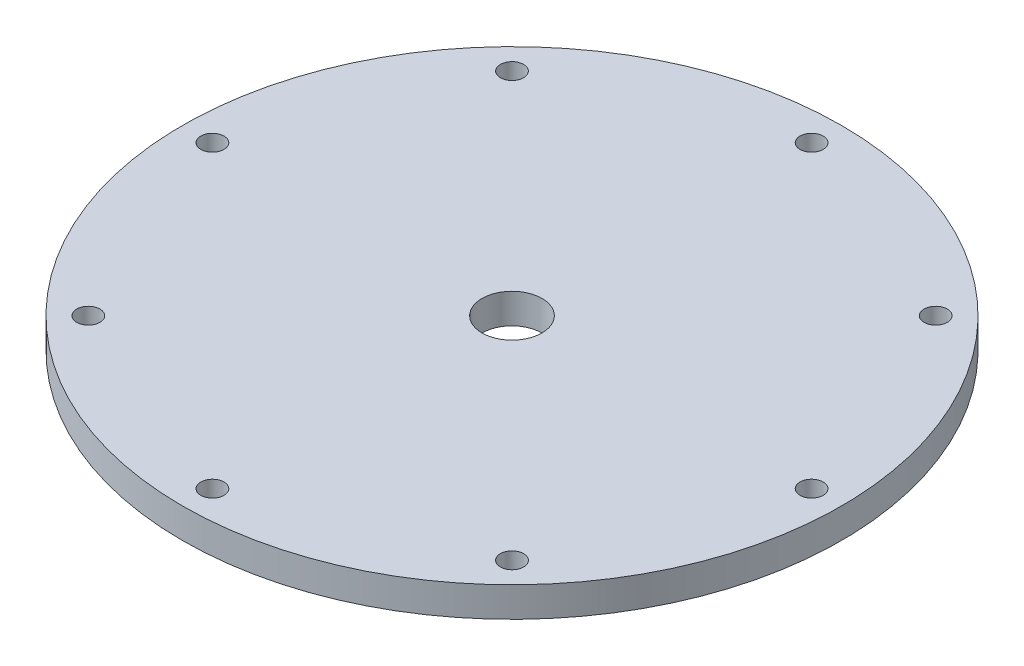
SolidWorks part; units mm, degrees
material "AISI 316 Stainless Steel Sheet (SS)"
ref_plane "Front Plane" through (0, 0, 0) normal (0, 0, 1) x (1, 0, 0)
ref_plane "Top Plane" through (0, 0, 0) normal (0, 1, 0) x (1, 0, 0)
ref_plane "Right Plane" through (0, 0, 0) normal (1, 0, 0) x (0, 0, -1)
sketch "Sketch1" plane through (0, 0, 0) normal (0, 1, 0) x (1, 0, 0)
  circle A0 centre (0, 0) radius 6.35
  circle A1 centre (0, 0) radius 69.85
  dimension "D1" = 12.7
  dimension "D2" = 139.7
extrude "Boss-Extrude1" add sketch "Sketch1" along normal blind 6.35
hole_wizard "#10 (0.1935) Diameter Hole1" positions "3DSketch2" profile "Sketch3" hole size "#10" standard "ANSI Inch" end condition through all
sketch3d "3DSketch2"
  line L0 (0, 0, 0) -> (63.5, 0, 0) construction
  point P9 (63.5, 0, 0)
  dimension "D1" = 63.5
sketch "Sketch3" plane through (63.5, 0, 0) normal (1, 0, 0) x (0, 0, -1)
  line L0 (0, 0) -> (0, 6.35)
  line L1 (0, 6.35) -> (2.4574, 6.35)
  line L2 (2.4574, 6.35) -> (2.4574, 0)
  line L5 (2.4574, 0) -> (0, 0)
  line L11 (0, -6.35) -> (0, 107.95) construction
  dimension "Thru Hole Dia." = 4.9149
  dimension "Thru Hole Depth" = 6.35
pattern_circular "CirPattern1" count 8 over 360 about axis through (0, 6.35, 0) along (0, -1, 0) of "#10 (0.1935) Diameter Hole1" reverse direction yes
